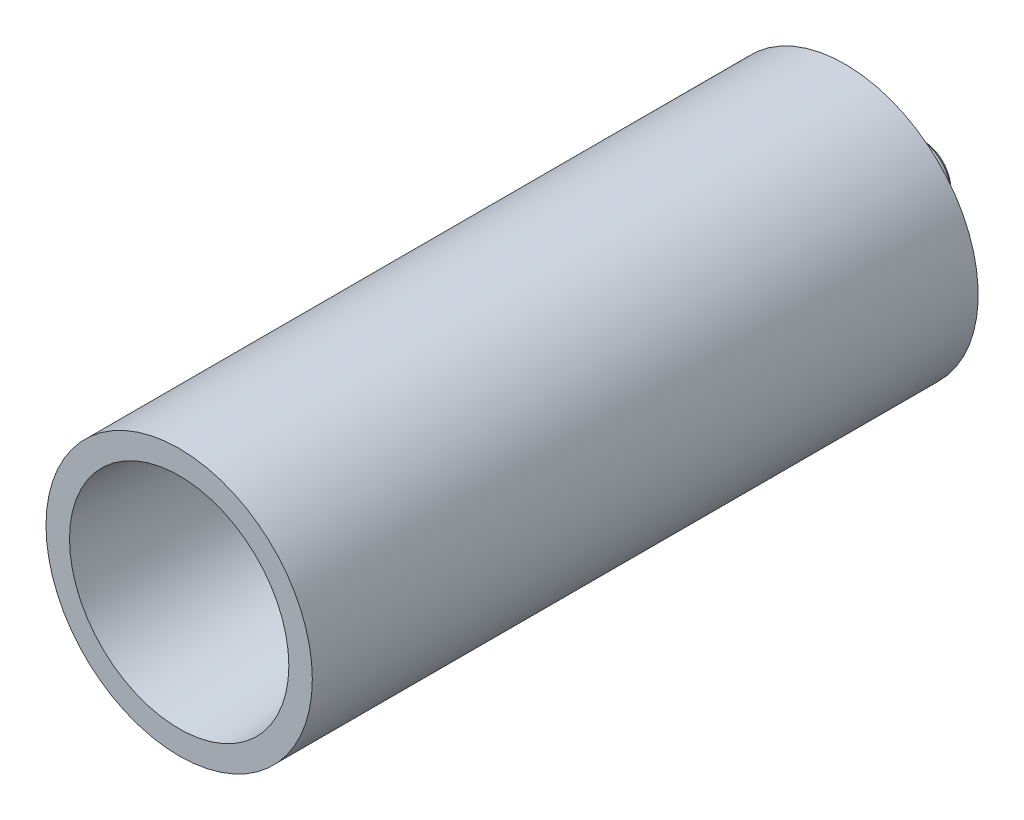
SolidWorks part; units mm, degrees
ref_plane "Front Plane" through (0, 0, 0) normal (0, 0, 1) x (1, 0, 0)
ref_plane "Top Plane" through (0, 0, 0) normal (0, 1, 0) x (1, 0, 0)
ref_plane "Right Plane" through (0, 0, 0) normal (1, 0, 0) x (0, 0, -1)
sketch "Sketch1" plane through (0, 0, 0) normal (0, 0, 1) x (1, 0, 0)
  circle A0 centre (0, 0) radius 17
  circle A1 centre (0, 0) radius 12
  dimension "D1" = 24
  dimension "D2" = 5
extrude "Boss-Extrude1" add sketch "Sketch1" along normal blind 80
chamfer "Chamfer1" distance 2 angle 85 1 edges at (12, 0, 80) first distance on face at (17, 0, 80)
sketch "Sketch2" plane through (0, 0, 0) normal (0, 0, -1) x (-1, 0, 0)
  circle A0 centre (0, 0) radius 17 construction
  circle A1 centre (0, 0) radius 17
extrude "Boss-Extrude2" add sketch "Sketch2" along normal blind 5
sketch "Sketch3" plane through (0, 0, -5) normal (0, 0, -1) x (-1, 0, 0)
  circle A0 centre (0, 0) radius 4
  circle A1 centre (0, 0) radius 9
  dimension "D1" = 8
  dimension "D2" = 5
extrude "Boss-Extrude3" add sketch "Sketch3" along normal blind 3 contours A0 | A1 A0 region at (0, 0, -5) region at (8.7454, 0, -5)
extrude "Boss-Extrude4" add sketch "Sketch3<3>" along normal blind 7 from surface contours A0 starting at face at (-9, 0, -8)
sketch "Sketch3<3>" plane through (0, 0, -5) normal (0, 0, -1) x (-1, 0, 0) same geometry as "Sketch3"
fillet "Fillet1" radius 12 1 edges at (-9, 0, -5)
chamfer "Chamfer2" distance 0.5 angle 45 1 edges at (-4, 0, -15)
